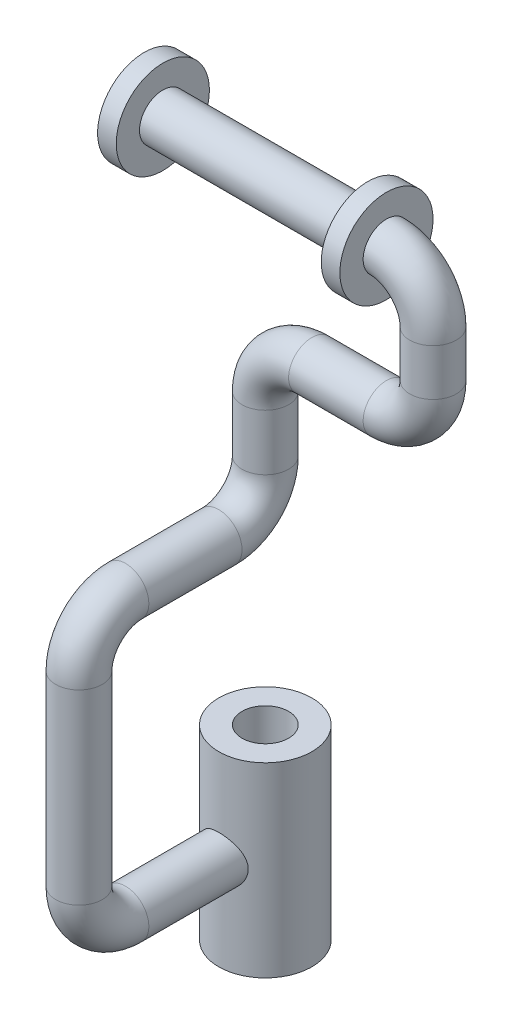
SolidWorks part; units mm, degrees
ref_plane "Plan de face" through (0, 0, 0) normal (0, 0, 1) x (1, 0, 0)
ref_plane "Plan de dessus" through (0, 0, 0) normal (0, 1, 0) x (1, 0, 0)
ref_plane "Plan de droite" through (0, 0, 0) normal (1, 0, 0) x (0, 0, -1)
sketch "Esquisse1" plane through (0, 0, 0) normal (0, 0, 1) x (1, 0, 0)
  line L0 (18, -15) -> (26, -15)
  line L1 (31, -10) -> (31, -5)
  line L2 (26, 0) -> (0, 0)
  line L3 (13, -20) -> (13, -25)
  arc A0 (26, -15) -> (31, -10) centre (26, -10) ccw
  arc A1 (31, -5) -> (26, 0) centre (26, -5) ccw
  arc A2 (13, -20) -> (18, -15) centre (18, -20) cw
  point P9 (31, -15)
  point P15 (13, -15)
  dimension "D5" = 5
  dimension "D6" = 5
  dimension "D1" = 15
  dimension "D2" = 31
  dimension "D3" = 10
  dimension "D4" = 18
ref_plane "Plan1" through (0, 0, 0) normal (1, 0, 0) x (0, 0, -1)
sketch "Esquisse2" plane through (0, 0, 0) normal (1, 0, 0) x (0, 0, -1)
  circle A0 centre (0, 0) radius 2.5
  dimension "D1" = 5
sweep "Balayage1" add profiles "Esquisse2" path "Esquisse1"
sketch "Esquisse6" plane through (0, 0, 0) normal (1, 0, 0) x (0, 0, -1)
  circle A0 centre (0, 0) radius 2.5 construction
  circle A1 centre (0, 0) radius 5
  dimension "D2" = 10
extrude "Boss.-Extru.2" add sketch "Esquisse6" along normal blind 2
ref_plane "Plan2" through (26, 0, 0) normal (1, 0, 0) x (0, 0, -1)
sketch "Esquisse7" plane through (26, 0, 0) normal (1, 0, 0) x (0, 0, -1)
  circle A1 centre (0, 0) radius 5
  dimension "D2" = 10
extrude "Boss.-Extru.3" add sketch "Esquisse7" against normal blind 2
ref_point "Point1"
ref_plane "Plan3" through (13, 0, 0) normal (1, 0, 0) x (0, 0, -1)
sketch "Esquisse8" plane through (13, 0, 0) normal (1, 0, 0) x (0, 0, -1)
  line L0 (0, -25) -> (0, -26)
  line L1 (-5, -31) -> (-15, -31)
  line L2 (-20, -36) -> (-20, -56)
  line L3 (-15, -61) -> (0, -61)
  arc A0 (-20, -56) -> (-15, -61) centre (-15, -56) ccw
  arc A1 (0, -26) -> (-5, -31) centre (-5, -26) cw
  arc A2 (-15, -31) -> (-20, -36) centre (-15, -36) ccw
  point P9 (-20, -61)
  point P12 (0, -31)
  point P15 (-20, -31)
  dimension "D5" = 5
  dimension "D6" = 5
  dimension "D1" = 20
  dimension "D2" = 30
  dimension "D3" = 20
  dimension "D4" = 6
sketch "Esquisse9" plane through (0, -25, 0) normal (0, -1, 0) x (-1, 0, 0)
  circle A0 centre (-13, 0) radius 2.5
  dimension "D1" = 5
sweep "Balayage2" add profiles "Esquisse9" path "Esquisse8"
ref_point "Point2"
ref_plane "Plan4" through (0, -61, 0) normal (0, 1, 0) x (1, 0, 0)
sketch "Esquisse10" plane through (100.5, -61, 0) normal (0, -1, 0) x (0, 0, -1)
  line L0 (0, -90) -> (0, -85) construction
  circle A0 centre (0, -87.5) radius 5
  dimension "D1" = 10
extrude "Boss.-Extru.4" add sketch "Esquisse10" along normal blind 10 and the other way blind 10
sketch "Esquisse11" plane through (0, -71, 0) normal (0, -1, 0) x (0, 0, -1)
  circle A0 centre (0, 13) radius 2.5
  dimension "D1" = 5
extrude "Enlèv. mat.-Extru.1" cut sketch "Esquisse11" against normal up to next
